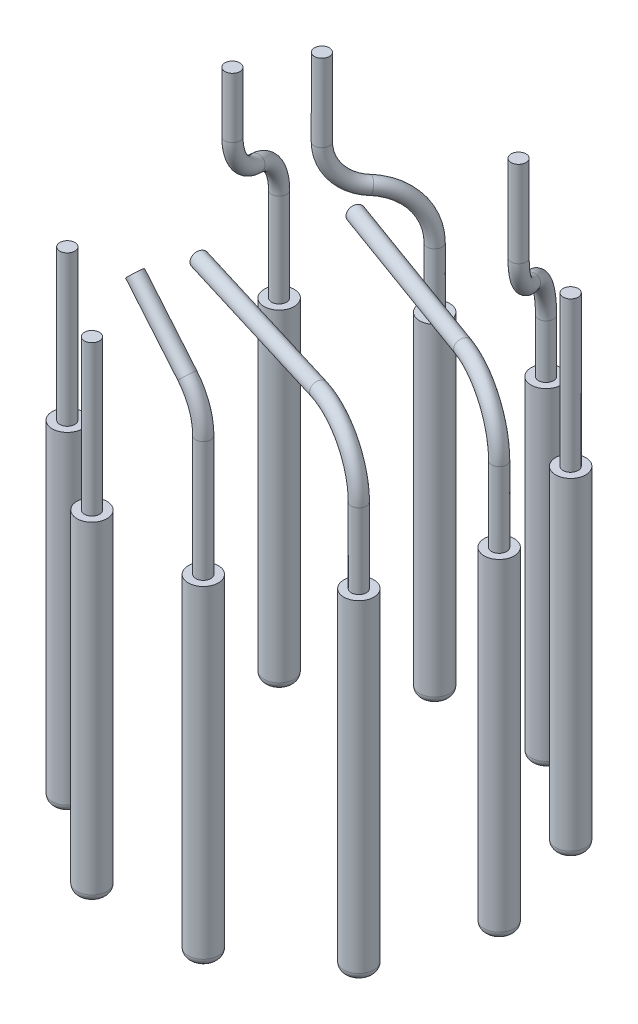
SolidWorks part; units mm, degrees
material "Chrome Stainless Steel"
ref_plane "Front Plane" through (0, 0, 0) normal (0, 0, 1) x (1, 0, 0)
ref_plane "Top Plane" through (0, 0, 0) normal (0, 1, 0) x (1, 0, 0)
ref_plane "Right Plane" through (0, 0, 0) normal (1, 0, 0) x (0, 0, -1)
sketch "Sketch1" plane through (0, 0, 0) normal (0, 1, 0) x (1, 0, 0)
  line L0 (-4.8541, 3.5267) -> (0, 0) construction
  line L1 (0, 0) -> (-1.8541, 5.7063) construction
  line L2 (0, 0) -> (1.8541, 5.7063) construction
  line L3 (4.8541, 3.5267) -> (0, 0) construction
  line L4 (4.8541, -3.5267) -> (0, 0) construction
  line L5 (0, 0) -> (1.8541, -5.7063) construction
  line L6 (-1.8541, -5.7063) -> (0, 0) construction
  line L7 (-4.8541, -3.5267) -> (0, 0) construction
  line L8 (-6.875, 0) -> (6.875, 0) construction
  circle A0 centre (0, 0) radius 6 construction
  circle A1 centre (6, 0) radius 0.5
  circle A2 centre (4.8541, -3.5267) radius 0.5
  circle A3 centre (1.8541, -5.7063) radius 0.5
  circle A4 centre (-1.8541, -5.7063) radius 0.5
  circle A5 centre (-4.8541, -3.5267) radius 0.5
  circle A7 centre (-4.8541, 3.5267) radius 0.5
  circle A8 centre (-1.8541, 5.7063) radius 0.5
  circle A9 centre (1.8541, 5.7063) radius 0.5
  circle A10 centre (4.8541, 3.5267) radius 0.5
  dimension "D1" = 12
  dimension "D2" = 1
  dimension "D3" = 36
  dimension "D4" = 72
  dimension "D5" = 72
  dimension "D6" = 36
  dimension "D8" = 72
  dimension "D9" = 72
  dimension "D10" = 36
  dimension "D11" = 36
ref_axis "Axis1" [suppressed] through (0, -7.05, 0) along (0, 1, 0)
extrude "Extrude2" add sketch "Sketch1" against normal blind 6.5 and the other way blind 4.5
ref_plane "Plane1" through (0, 4.5, 0) normal (0, 1, 0) x (-1, 0, 0)
sketch "Sketch3" plane through (0, 4.5, 0) normal (0, 1, 0) x (-1, 0, 0)
  circle A0 centre (4.8541, 3.5267) radius 0.25
  circle A1 centre (1.8541, 5.7063) radius 0.25
  circle A2 centre (-4.8541, -3.5267) radius 0.25
  dimension "D1" = 0.5
extrude "Extrude3" add sketch "Sketch3" along normal blind 5
ref_plane "base of lower mica" through (0, 13, 0) normal (0, 1, 0) x (-1, 0, 0)
fillet "Fillet1" radius 0.25 1 edges at (4.8541, -6.5, -3.0267)
fillet "Fillet2" radius 0.25 1 edges at (1.8541, -6.5, -5.2063)
fillet "Fillet3" radius 0.25 1 edges at (-1.8541, -6.5, -5.2063)
fillet "Fillet4" radius 0.25 1 edges at (-4.8541, -6.5, -3.0267)
fillet "Fillet5" radius 0.25 1 edges at (-4.8541, -6.5, 4.0267)
fillet "Fillet6" radius 0.25 1 edges at (-1.8541, -6.5, 6.2063)
fillet "Fillet7" radius 0.25 1 edges at (1.8541, -6.5, 6.2063)
fillet "Fillet8" radius 0.25 1 edges at (4.8541, -6.5, 4.0267)
fillet "Fillet9" radius 0.25 1 edges at (6, -6.5, 0.5)
ref_axis "Axis2" through (1.8541, 4.5, 5.7063) along (0, -1, 0)
ref_plane "Plane3" through (-0.4814, 0, 5.502) normal (-0.0872, 0, 0.9962) x (0.9962, 0, 0.0872)
sketch "Sketch4" plane through (-0.4814, 0, 5.502) normal (-0.0872, 0, 0.9962) x (0.9962, 0, 0.0872)
  line L0 (2.3444, 4.5) -> (2.3444, 8.5)
  line L1 (6.5198, 4.5) -> (-6.5198, 4.5) construction
  line L2 (2.3444, 4.5) -> (2.3444, -6.25) construction
  line L3 (1.7586, 9.9142) -> (-0.1556, 11.8284)
  arc A0 (2.3444, 8.5) -> (1.7586, 9.9142) centre (0.3444, 8.5) ccw
  point P9 (2.3444, 9.3284)
  dimension "D1" = 2
  dimension "D2" = 4
  dimension "D3" = 2.5
  dimension "D4" = 135
sketch "Sketch5" plane through (0, 4.5, 0) normal (0, 1, 0) x (-1, 0, 0)
  circle A0 centre (-1.8541, 5.7063) radius 0.25
  dimension "D1" = 0.5
sweep "Sweep1" add profiles "Sketch5" path "Sketch4"
ref_axis "Axis3" through (4.8541, 4.5, 3.5267) along (0, -1, 0)
ref_axis "Axis4" through (6, 4.5, 0) along (0, -1, 0)
ref_plane "Plane4" through (0.7019, 0, -1.9284) normal (-0.342, 0, 0.9397) x (0.9397, 0, 0.342)
ref_plane "Plane5" through (-0.5711, 0, 1.8681) normal (-0.2924, 0, 0.9563) x (0.9563, 0, 0.2924)
sketch "Sketch6" plane through (-0.5711, 0, 1.8681) normal (-0.2924, 0, 0.9563) x (0.9563, 0, 0.2924)
  line L0 (5.6731, 4.5) -> (5.6731, 7)
  line L1 (6.1731, 4.5) -> (5.1731, 4.5) construction
  line L2 (5.6731, 4.5) -> (5.6731, -6.25) construction
  line L3 (3.6731, 9) -> (-2.3269, 9)
  arc A0 (5.6731, 7) -> (3.6731, 9) centre (3.6731, 7) ccw
  point P9 (5.6731, 9)
  dimension "D3" = 2
  dimension "D1" = 4.5
  dimension "D2" = 8
sketch "Sketch7" plane through (0, 4.5, 0) normal (0, 1, 0) x (-1, 0, 0)
  circle A0 centre (-4.8541, 3.5267) radius 0.25
  dimension "D1" = 0.5
sweep "Sweep2" add profiles "Sketch7" path "Sketch6"
sketch "Sketch8" plane through (0.7019, 0, -1.9284) normal (-0.342, 0, 0.9397) x (0.9397, 0, 0.342)
  line L0 (5.6382, 4.5) -> (5.6382, 7)
  line L1 (6.5198, 4.5) -> (-6.5198, 4.5) construction
  line L2 (5.6382, 4.5) -> (5.6382, -6.25) construction
  line L3 (3.6382, 9) -> (-2.3618, 9)
  arc A0 (5.6382, 7) -> (3.6382, 9) centre (3.6382, 7) ccw
  point P9 (5.6382, 9)
  dimension "D1" = 2
  dimension "D2" = 4.5
  dimension "D3" = 8
sketch "Sketch9" plane through (0, 4.5, 0) normal (0, 1, 0) x (-1, 0, 0)
  circle A0 centre (-6, 0) radius 0.25
  dimension "D1" = 0.5
sweep "Sweep3" add profiles "Sketch9" path "Sketch8"
ref_axis "Axis5" through (1.8541, 4.5, -5.7063) along (0, -1, 0)
ref_plane "Plane6" through (3.8615, 0, -2.2294) normal (0.866, 0, -0.5) x (-0.5, 0, -0.866)
sketch "Sketch10" plane through (3.8615, 0, -2.2294) normal (0.866, 0, -0.5) x (-0.5, 0, -0.866)
  line L0 (4.0148, 4.5) -> (4.0148, 6.2756)
  line L1 (4.0148, 4.5) -> (4.0148, -6.25) construction
  line L2 (6.5198, 4.5) -> (-6.5198, 4.5) construction
  line L4 (1.5148, 9.6297) -> (1.5148, 12.5)
  arc A0 (4.0148, 6.2756) -> (2.5862, 8.1923) centre (2.0148, 6.2756) ccw
  arc A1 (1.5148, 9.6297) -> (2.5862, 8.1923) centre (3.0148, 9.6297) ccw
  point P10 (4.0148, 8.2756)
  dimension "D3" = 2
  dimension "D1" = 1.5
  dimension "D2" = 8
  dimension "D4" = 2.5
sketch "Sketch12" plane through (0, 4.5, 0) normal (0, 1, 0) x (1, 0, 0)
  circle A0 centre (1.8541, 5.7063) radius 0.25
  dimension "D1" = 0.5
sweep "Sweep4" add profiles "Sketch12" path "Sketch10"
ref_axis "Axis6" through (-1.8541, 4.5, -5.7063) along (0, -1, 0)
ref_plane "Plane7" through (-3.8615, 0, -2.2294) normal (0.866, 0, 0.5) x (0.5, 0, -0.866)
sketch "Sketch13" plane through (-3.8615, 0, -2.2294) normal (0.866, 0, 0.5) x (0.5, 0, -0.866)
  line L0 (4.0148, 4.5) -> (4.0148, 6.5)
  line L1 (6.5198, 4.5) -> (-6.5198, 4.5) construction
  line L2 (4.0148, 4.5) -> (4.0148, -6.25) construction
  line L4 (1.2648, 9.9187) -> (1.2648, 12.5)
  arc A0 (4.0148, 6.5) -> (2.4434, 8.4535) centre (2.0148, 6.5) ccw
  arc A1 (1.2648, 9.9187) -> (2.4434, 8.4535) centre (2.7648, 9.9187) ccw
  point P10 (4.0148, 7.2378)
  dimension "D1" = 2
  dimension "D2" = 1.5
  dimension "D3" = 2.75
  dimension "D4" = 2
  dimension "D5" = 8
sketch "Sketch14" plane through (0, 4.5, 0) normal (0, 1, 0) x (1, 0, 0)
  circle A0 centre (-1.8541, 5.7063) radius 0.25
  dimension "D1" = 0.5
sweep "Sweep5" add profiles "Sketch14" path "Sketch13"
ref_axis "Axis7" through (-4.8541, 4.5, -3.5267) along (0, -1, 0)
ref_plane "Plane8" through (-3.6473, 0, 0.9773) normal (-0.9659, 0, 0.2588) x (0.2588, 0, 0.9659)
sketch "Sketch15" plane through (-3.6473, 0, 0.9773) normal (-0.9659, 0, 0.2588) x (0.2588, 0, 0.9659)
  line L0 (-4.6629, 4.5) -> (-4.6629, 7.6086)
  line L1 (6.5198, 4.5) -> (-6.5198, 4.5) construction
  line L2 (-4.6629, 4.5) -> (-4.6629, -6.25) construction
  line L4 (-2.4629, 10.5) -> (-2.4629, 12.5)
  arc A0 (-3.5629, 9.0543) -> (-4.6629, 7.6086) centre (-3.1629, 7.6086) ccw
  arc A1 (-2.4629, 10.5) -> (-3.5629, 9.0543) centre (-3.9629, 10.5) cw
  point P10 (-4.6629, 8.5)
  dimension "D3" = 1.5
  dimension "D4" = 1.5
  dimension "D1" = 8
  dimension "D2" = 4
  dimension "D5" = 2.2
  dimension "D6" = 2
sketch "Sketch16" plane through (0, 4.5, 0) normal (0, 1, 0) x (1, 0, 0)
  circle A0 centre (-4.8541, 3.5267) radius 0.25
  dimension "D1" = 0.5
sweep "Sweep6" add profiles "Sketch16" path "Sketch15"
